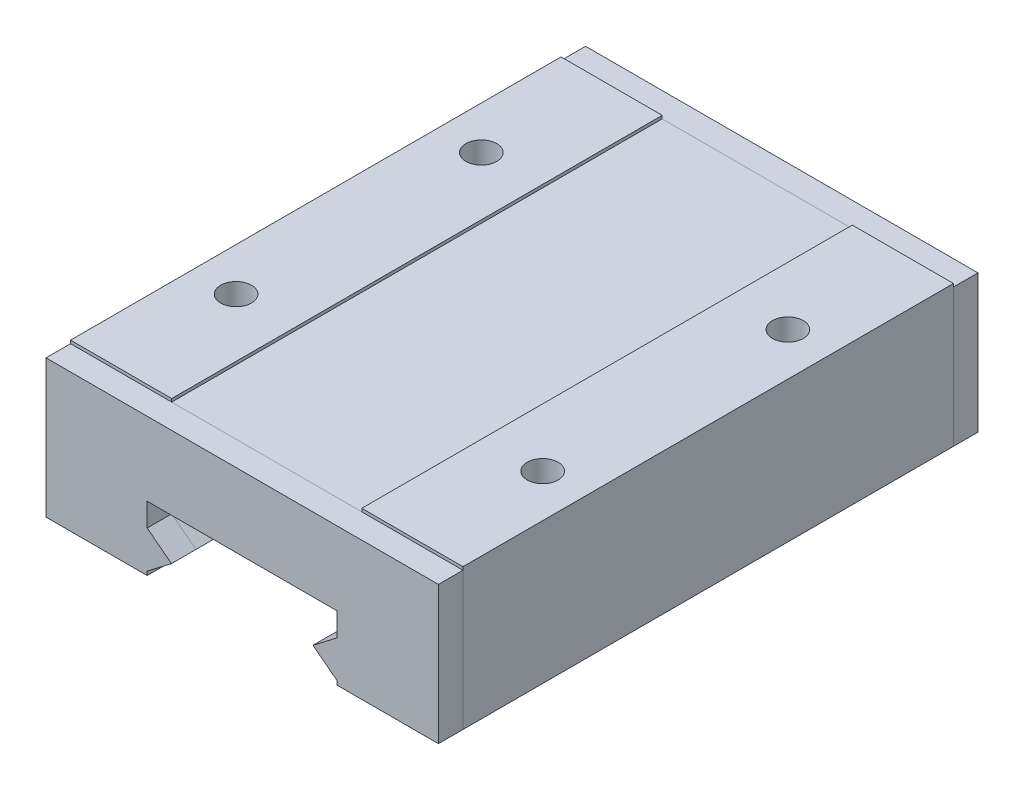
SolidWorks part; units mm, degrees
ref_plane "Front Plane" through (0, 0, 0) normal (0, 0, 1) x (1, 0, 0)
ref_plane "Top Plane" through (0, 0, 0) normal (0, 1, 0) x (1, 0, 0)
ref_plane "Right Plane" through (0, 0, 0) normal (1, 0, 0) x (0, 0, -1)
sketch "Sketch3" plane through (0, 0, 0) normal (0, 0, 1) x (1, 0, 0)
  line L0 (0, -1.3402) -> (0, 9.5975) construction
  line L1 (-16, 16) -> (-7.75, 16)
  line L2 (-16, 16) -> (-16, 4.5)
  line L3 (-16, 4.5) -> (-7.75, 4.5)
  line L4 (16, 16) -> (16, 4.5)
  line L5 (-7.5452, 6.3333) -> (3.7641, 6.3333) construction
  line L7 (-7.5, 0) -> (7.5, 0) construction
  line L8 (-7.75, 4.5) -> (-7.75, 4.8123)
  line L9 (-5.7678, 6.3333) -> (-7.75, 4.8123)
  line L10 (-7.5, 9.5) -> (7.5, 9.5) construction
  line L11 (7.5, 7.9776) -> (5.3571, 6.3333) construction
  line L12 (7.5, 7.9776) -> (7.5, 9.5) construction
  line L13 (-7.75, 7.8543) -> (-5.7678, 6.3333)
  line L14 (-7.75, 7.8543) -> (-7.75, 9.75)
  line L15 (-7.75, 9.75) -> (7.75, 9.75)
  line L16 (7.75, 7.8543) -> (7.75, 9.75)
  line L17 (7.75, 7.8543) -> (5.7678, 6.3333)
  line L18 (-7.5, 7.9776) -> (-7.5, 9.5) construction
  line L19 (-7.5, 7.9776) -> (-5.3571, 6.3333) construction
  line L20 (-5.3571, 6.3333) -> (-7.5, 4.6891) construction
  line L21 (-7.5, 0) -> (-7.5, 4.6891) construction
  line L22 (7.5, 0) -> (7.5, 4.6891) construction
  line L23 (5.7678, 6.3333) -> (7.75, 4.8123)
  line L24 (5.3571, 6.3333) -> (7.5, 4.6891) construction
  line L25 (7.75, 4.5) -> (7.75, 4.8123)
  line L39 (7.75, 4.5) -> (16, 4.5)
  line L41 (7.75, 16) -> (16, 16)
  line L43 (-7.75, 16) -> (-7.75, 15.75)
  line L44 (-7.75, 15.75) -> (7.75, 15.75)
  line L45 (7.75, 16) -> (7.75, 15.75)
  dimension "Height [B1]" = 11.5
  dimension "Width [B]" = 32
  dimension "D6" = 0.25
  dimension "Height [H]" = 16
  dimension "Width [C]" = 15
  dimension "D3" = 3.1667
  dimension "D4" = 75
  dimension "D5" = 2.1429
  dimension "Height [H1]" = 9.5
  dimension "Width [W]" = 8.5
  dimension "D7" = 0.25
extrude "Carriage" add sketch "Sketch3" along normal mid plane 40
sketch "Sketch4" plane through (0, 0, 20) normal (0, 0, 1) x (1, 0, 0)
  line L0 (-16, 15.75) -> (16, 15.75)
  line L2 (7.75, 15.75) -> (-7.75, 15.75) construction
  line L19 (-16, 16) -> (-16, 4.5)
  line L20 (-16, 4.5) -> (-7.75, 4.5)
  line L21 (-7.75, 4.5) -> (-7.75, 4.8123)
  line L22 (-7.75, 4.8123) -> (-5.7678, 6.3333)
  line L23 (-5.7678, 6.3333) -> (-7.75, 7.8543)
  line L24 (-7.75, 7.8543) -> (-7.75, 9.75)
  line L25 (-7.75, 9.75) -> (7.75, 9.75)
  line L26 (7.75, 9.75) -> (7.75, 7.8543)
  line L27 (7.75, 7.8543) -> (5.7678, 6.3333)
  line L28 (5.7678, 6.3333) -> (7.75, 4.8123)
  line L29 (7.75, 4.8123) -> (7.75, 4.5)
  line L30 (7.75, 4.5) -> (16, 4.5)
  line L31 (16, 4.5) -> (16, 16)
  line L32 (16, 16) -> (7.75, 16)
  line L33 (7.75, 16) -> (7.75, 15.75)
  line L34 (7.75, 15.75) -> (-7.75, 15.75)
  line L35 (-7.75, 15.75) -> (-7.75, 16)
  line L36 (-7.75, 16) -> (-16, 16)
  line L37 (-16, 15.75) -> (-16, 4.5)
  line L38 (-16, 4.5) -> (-7.75, 4.5)
  line L39 (-7.75, 4.5) -> (-7.75, 4.8123)
  line L40 (-7.75, 4.8123) -> (-5.7678, 6.3333)
  line L41 (-5.7678, 6.3333) -> (-7.75, 7.8543)
  line L42 (-7.75, 7.8543) -> (-7.75, 9.75)
  line L43 (-7.75, 9.75) -> (7.75, 9.75)
  line L44 (7.75, 9.75) -> (7.75, 7.8543)
  line L45 (7.75, 7.8543) -> (5.7678, 6.3333)
  line L46 (5.7678, 6.3333) -> (7.75, 4.8123)
  line L47 (7.75, 4.8123) -> (7.75, 4.5)
  line L48 (7.75, 4.5) -> (16, 4.5)
  line L49 (16, 4.5) -> (16, 15.75)
  dimension "D1" = 0
extrude "Side-seal1" add sketch "Sketch4" along normal blind 2 separate body
ref_plane "Plane2" through (0, 0, -22) normal (0, 0, 1) x (1, 0, 0)
sketch "Sketch5" plane through (0, 0, -22) normal (0, 0, 1) x (1, 0, 0)
  line L8 (-16, 4.5) -> (-7.75, 4.5)
  line L9 (-16, 4.5) -> (-7.75, 4.5)
  line L10 (-7.75, 4.5) -> (-7.75, 4.8123)
  line L11 (-7.75, 4.5) -> (-7.75, 4.8123)
  line L12 (-7.75, 4.8123) -> (-5.7678, 6.3333)
  line L13 (-7.75, 4.8123) -> (-5.7678, 6.3333)
  line L14 (-5.7678, 6.3333) -> (-7.75, 7.8543)
  line L15 (-5.7678, 6.3333) -> (-7.75, 7.8543)
  line L16 (-7.75, 7.8543) -> (-7.75, 9.75)
  line L17 (-7.75, 7.8543) -> (-7.75, 9.75)
  line L18 (-7.75, 9.75) -> (7.75, 9.75)
  line L19 (-7.75, 9.75) -> (7.75, 9.75)
  line L20 (7.75, 9.75) -> (7.75, 7.8543)
  line L21 (7.75, 9.75) -> (7.75, 7.8543)
  line L22 (7.75, 7.8543) -> (5.7678, 6.3333)
  line L23 (7.75, 7.8543) -> (5.7678, 6.3333)
  line L30 (5.7678, 6.3333) -> (7.75, 4.8123)
  line L31 (5.7678, 6.3333) -> (7.75, 4.8123)
  line L32 (7.75, 4.8123) -> (7.75, 4.5)
  line L33 (7.75, 4.8123) -> (7.75, 4.5)
  line L34 (7.75, 4.5) -> (16, 4.5)
  line L35 (7.75, 4.5) -> (16, 4.5)
  line L36 (16, 4.5) -> (16, 15.75)
  line L37 (16, 4.5) -> (16, 15.75)
  line L38 (16, 15.75) -> (-16, 15.75)
  line L39 (16, 15.75) -> (-16, 15.75)
  line L40 (-16, 15.75) -> (-16, 4.5)
  line L41 (-16, 15.75) -> (-16, 4.5)
  dimension "D1" = 0
extrude "Side-seal2" add sketch "Sketch5" along normal up to surface (2 mm away) separate body up to face at (0, 9.5, -20)
sketch "Sketch11" plane through (0, 16, 0) normal (0, 1, 0) x (-1, 0, 0)
  line L0 (-15.0071, 0) -> (14.8228, 0) construction
  line L2 (-7.75, 20) -> (7.75, 20) construction
  line L4 (0, 20.6756) -> (0, -23.794) construction
  line L5 (-16, 20) -> (-16, -20) construction
  line L6 (16, 20) -> (16, -20) construction
  line L7 (-7.75, -20) -> (7.75, -20) construction
  circle A0 centre (-12.5, 10) radius 1.26
  circle A1 centre (12.5, 10) radius 1.26
  circle A2 centre (12.5, -10) radius 1.26
  circle A3 centre (-12.5, -10) radius 1.26
  dimension "Thread [S1]" = 2.52
  dimension "Spacing [P2]" = 20
  dimension "Spacing [P1]" = 25
extrude "Hole" cut sketch "Sketch11" against normal blind 4
cosmetic thread "Cosmetic Thread6" parameters "D2"=3.02
cosmetic thread "Cosmetic Thread7" parameters "D2"=3.02
cosmetic thread "Cosmetic Thread8" parameters "D2"=3.02
cosmetic thread "Cosmetic Thread9" parameters "D2"=3.02
equation "\"D1@Side-seal1\"=(\"Length [L2]@Plane2\"-\"Length [L1]@Carriage\")/2"
equation "\"D3@Sketch3\" = \"Height [H1]@Sketch3\"/3"
equation "\"D5@Sketch3\"=\"Width [C]@Sketch3\"/7"
equation "\"D2@Cosmetic Thread6\" = \"Thread [S1]@Sketch11\"+.5"
equation "\"D2@Cosmetic Thread7\" = \"Thread [S1]@Sketch11\"+.5"
equation "\"D2@Cosmetic Thread8\" = \"Thread [S1]@Sketch11\"+.5"
equation "\"D2@Cosmetic Thread9\" = \"Thread [S1]@Sketch11\"+.5"
